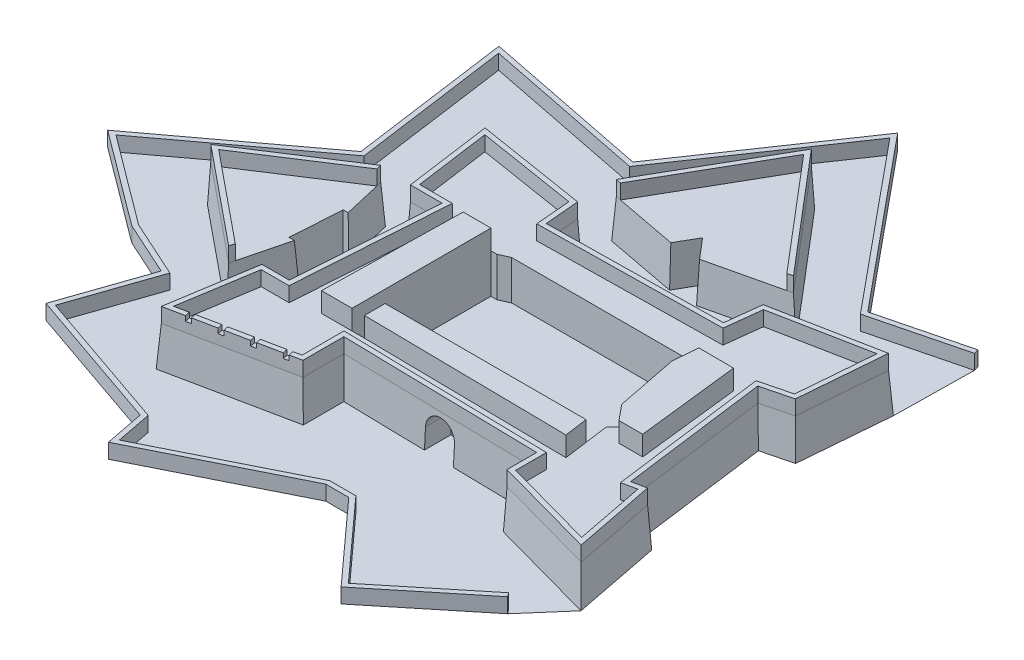
SolidWorks part; units mm, degrees
note: The reader was unsure of these and kept them because the rebuilt part matched: shared geometry of "Sketch5<4>", "Sketch5<6>", "Sketch7<4>", "Sketch7<6>".
material "Ceramic Porcelain"
ref_plane "Front Plane" through (0, 0, 0) normal (0, 0, 1) x (1, 0, 0)
ref_plane "Top Plane" through (0, 0, 0) normal (0, 1, 0) x (1, 0, 0)
ref_plane "Right Plane" through (0, 0, 0) normal (1, 0, 0) x (0, 0, -1)
sketch "Sketch5" plane through (0, 0, 0) normal (0, 1, 0) x (1, 0, 0)
  line L0 (24221.1472, 12812.7772) -> (25709.497, 22090.1576)
  line L1 (25709.497, 22090.1576) -> (28473.8169, 22090.1576)
  line L2 (28473.8169, 22090.1576) -> (29430.1682, 36196.3384)
  line L3 (29430.1682, 36196.3384) -> (26254.1998, 36196.3384)
  line L4 (26254.1998, 36196.3384) -> (24972.577, 45446.6988)
  line L5 (24972.577, 45446.6988) -> (36613.3827, 43579.1898)
  line L6 (36613.3827, 43579.1898) -> (36920.5122, 40112.6097)
  line L7 (36920.5122, 40112.6097) -> (54258.5673, 40378.764)
  line L8 (54258.5673, 40378.764) -> (54681.4749, 43954.2552)
  line L9 (54681.4749, 43954.2552) -> (65747.3221, 46120.0937)
  line L10 (65747.3221, 46120.0937) -> (64980.7856, 36956.7795)
  line L11 (64980.7856, 36956.7795) -> (61977.0436, 36196.3384)
  line L12 (61977.0436, 36196.3384) -> (63878.1461, 21747.9592)
  line L13 (63878.1461, 21747.9592) -> (65285.6599, 22049.5692)
  line L14 (65285.6599, 22049.5692) -> (67033.9764, 13116.9536)
  line L15 (67033.9764, 13116.9536) -> (56159.6698, 16120.6957)
  line L16 (56159.6698, 16120.6957) -> (56159.6698, 19081.3266)
  line L17 (56159.6698, 19081.3266) -> (36613.3827, 19466.6361)
  line L18 (36613.3827, 19466.6361) -> (36613.3827, 15360.2546)
  line L19 (36613.3827, 15360.2546) -> (24221.1472, 12812.7772)
  line L20 (-1773.6346, 178.1498) -> (-1176.968, 178.1498) construction
  line L21 (22700.2652, 21443.7828) -> (12396.2895, 29846.656)
  line L22 (12396.2895, 29846.656) -> (23346.6401, 36956.7795)
  line L23 (23346.6401, 36956.7795) -> (24487.3016, 32089.957)
  line L24 (24487.3016, 32089.957) -> (23916.9708, 32089.957)
  line L25 (23916.9708, 32089.957) -> (23612.7944, 27337.2006)
  line L26 (23612.7944, 27337.2006) -> (24202.1362, 27337.2006)
  line L27 (24202.1362, 27337.2006) -> (22700.2652, 21443.7828)
  line L28 (36084.0271, 47184.7111) -> (43604.7887, 60268.0988)
  line L29 (43604.7887, 60268.0988) -> (54258.5673, 47720.822)
  line L30 (54258.5673, 47720.822) -> (46076.764, 45803.2119)
  line L31 (46076.764, 45803.2119) -> (44448.5387, 47720.822)
  line L32 (44448.5387, 47720.822) -> (43346.2333, 45803.2119)
  line L33 (43346.2333, 45803.2119) -> (36084.0271, 47184.7111)
  line L34 (54258.5673, 1546.8436) -> (63580.1829, 9139.4247)
  line L35 (54258.5673, 1546.8436) -> (46779.4578, 9805.0782)
  line L36 (46779.4578, 9805.0782) -> (44448.5387, 9805.0782)
  line L37 (44448.5387, 9805.0782) -> (29734.3446, 2459.3728)
  line L38 (29734.3446, 2459.3728) -> (28951.9926, 6456.6182)
  line L39 (28951.9926, 6456.6182) -> (14358.2273, 11493.4121)
  line L40 (14358.2273, 11493.4121) -> (15582.0398, 15039.3251)
  line L41 (15582.0398, 15039.3251) -> (17356.6178, 20181.0432)
  line L42 (17356.6178, 20181.0432) -> (11903.5237, 22658.2071)
  line L43 (11903.5237, 22658.2071) -> (2267.2151, 29846.656)
  line L44 (2267.2151, 29846.656) -> (16995.4367, 40821.5186)
  line L45 (16995.4367, 40821.5186) -> (14741.9326, 57086.6197)
  line L46 (14741.9326, 57086.6197) -> (31723.6583, 53702.451)
  line L47 (31723.6583, 53702.451) -> (42609.1401, 69687.8824)
  line L48 (42609.1401, 69687.8824) -> (56817.3793, 52446.1339)
  line L49 (56817.3793, 52446.1339) -> (65747.3221, 54706.8789)
  line L50 (56632.9822, 51883.6769) -> (65870.0331, 54222.1708)
  line L51 (31723.721, 22093.3415) -> (32001.7288, 36196.3384)
  line L52 (32001.7288, 36196.3384) -> (35428.9681, 36196.3384)
  line L53 (35428.9681, 36196.3384) -> (35428.9681, 22093.3415)
  line L54 (35428.9681, 22093.3415) -> (31723.721, 22093.3415)
  line L55 (36084.0271, 22093.3415) -> (36084.0271, 26560.0447)
  line L56 (36084.0271, 26560.0447) -> (56159.6698, 26560.0447)
  line L57 (56159.6698, 26560.0447) -> (56817.3793, 21812.8994)
  line L58 (56817.3793, 21812.8994) -> (36084.0271, 22093.3415)
  line L59 (60646.2718, 25773.5818) -> (58239.847, 25773.5818)
  line L60 (58239.847, 25773.5818) -> (56951.3309, 27337.2006)
  line L61 (56951.3309, 27337.2006) -> (55973.2334, 34396.8086)
  line L62 (55973.2334, 34396.8086) -> (55973.2334, 36196.3384)
  line L63 (55973.2334, 36196.3384) -> (59443.0594, 36196.3384)
  line L64 (59443.0594, 36196.3384) -> (60646.2718, 25773.5818)
  line L65 (35428.9681, 36196.3384) -> (36458.7307, 36657.9549)
  line L66 (36458.7307, 36657.9549) -> (54258.5673, 36657.9549)
  line L67 (54258.5673, 36657.9549) -> (55973.2334, 36196.3384)
  line L68 (56951.3309, 27337.2006) -> (56159.6698, 26560.0447)
  line L69 (36084.0271, 22093.3415) -> (35428.9681, 22093.3415)
  line L70 (42647.2108, 68855.4598) -> (56632.9822, 51883.6769)
  line L71 (31950.6039, 53147.3929) -> (42647.2108, 68855.4598)
  line L72 (15333.6835, 56458.862) -> (31950.6039, 53147.3929)
  line L73 (17531.2836, 40597.259) -> (15333.6835, 56458.862)
  line L74 (3103.7229, 29846.4364) -> (17531.2836, 40597.259)
  line L75 (12159.3372, 23091.1711) -> (3103.7229, 29846.4364)
  line L76 (17977.7189, 20448.069) -> (12159.3372, 23091.1711)
  line L77 (16054.6817, 14876.2006) -> (17977.7189, 20448.069)
  line L78 (14993.9937, 11802.9296) -> (16054.6817, 14876.2006)
  line L79 (29387.3629, 6835.299) -> (14993.9937, 11802.9296)
  line L80 (30098.8383, 3200.1815) -> (29387.3629, 6835.299)
  line L81 (44330.6682, 10305.0782) -> (30098.8383, 3200.1815)
  line L82 (47001.2063, 10305.0782) -> (44330.6682, 10305.0782)
  line L83 (54310.675, 2234.1565) -> (47001.2063, 10305.0782)
  line L84 (54310.675, 2234.1565) -> (63264.4166, 9527.0994)
  line L85 (65747.3221, 54706.8789) -> (65870.0331, 54222.1708)
  line L86 (63580.1829, 9139.4247) -> (63264.4166, 9527.0994)
  line L87 (63580.1829, 9139.4247) -> (67033.9764, 13116.9536)
  line L88 (65870.0331, 54222.1708) -> (65747.3221, 46120.0937)
  dimension "D1" = 19546.2871
  dimension "D2" = 500
extrude "Boss-Extrude2" add sketch "Sketch5" along normal blind 4000 draft 3 contours L19 L18 L17 L16 L15 L14 L13 L12 L11 L10 L9 L8 L7 L6 L5 L4 L3 L2 L1 L0 L58 L69 L54 L51 L52 L65 L66 L67 L63 L64 L59 L60 L68 L57 | L33 L32 L31 L30 L29 L28 | L27 L26 L25 L24 L23 L22 L21 | L69 L55 L56 L68 L61 L62 L67 L66 L65 L53 | L54 L53 L52 L51 | L58 L57 L56 L55 | L64 L63 L62 L61 L60 L59
extrude "Cut-Extrude8" cut sketch "Sketch5<4>" against normal blind 9000 and the other way through all contours L54 L53 L52 L51 | L69 L55 L56 L68 L61 L62 L67 L66 L65 L53 | L64 L63 L62 L61 L60 L59 | L58 L57 L56 L55
sketch "Sketch5<4>" plane through (0, 0, 0) normal (0, 1, 0) x (1, 0, 0) same geometry as "Sketch5"
extrude "Boss-Extrude8" add sketch "Sketch5<6>" along normal blind 1500 separate body contours L34 L86 L84 L83 L82 L81 L80 L79 L78 L77 L76 L75 L74 L73 L72 L71 L70 L50 L85 L49 L48 L47 L46 L45 L44 L43 L42 L41 L40 L39 L38 L37 L36 L35
sketch "Sketch5<6>" plane through (0, 0, 0) normal (0, 1, 0) x (1, 0, 0) same geometry as "Sketch5"
sketch "Sketch7" plane through (0, 0, 0) normal (0, 1, 0) x (1, 0, 0)
  line L0 (36412.5629, 47335.6038) -> (43238.8427, 46037.0314) construction
  line L1 (43238.8427, 46037.0314) -> (44415.3723, 48083.7647) construction
  line L2 (44415.3723, 48083.7647) -> (46153.6491, 46036.5437) construction
  line L3 (46153.6491, 46036.5437) -> (53876.7307, 47846.6409) construction
  line L4 (53876.7307, 47846.6409) -> (43637.955, 59905.1561) construction
  line L5 (43637.955, 59905.1561) -> (36412.5629, 47335.6038) construction
  line L6 (24476.2044, 13079.2242) -> (36403.7516, 15531.1754) construction
  line L7 (36403.7516, 15531.1754) -> (36403.7516, 19680.4403) construction
  line L8 (36403.7516, 19680.4403) -> (56369.301, 19286.866) construction
  line L9 (56369.301, 19286.866) -> (56369.301, 16280.2721) construction
  line L10 (56369.301, 16280.2721) -> (66763.1605, 13409.2409) construction
  line L11 (66763.1605, 13409.2409) -> (65120.9215, 21799.8781) construction
  line L12 (65120.9215, 21799.8781) -> (63699.9419, 21495.3825) construction
  line L13 (63699.9419, 21495.3825) -> (61744.8858, 36353.809) construction
  line L14 (61744.8858, 36353.809) -> (64784.3517, 37123.294) construction
  line L15 (64784.3517, 37123.294) -> (65515.2909, 45861.0713) construction
  line L16 (65515.2909, 45861.0713) -> (54871.7056, 43777.879) construction
  line L17 (54871.7056, 43777.879) -> (54445.2006, 40171.9732) construction
  line L18 (54445.2006, 40171.9732) -> (36728.8955, 39900.0124) construction
  line L19 (36728.8955, 39900.0124) -> (36418.9775, 43398.0662) construction
  line L20 (36418.9775, 43398.0662) -> (25219.1056, 45194.8371) construction
  line L21 (25219.1056, 45194.8371) -> (26436.7893, 36405.9696) construction
  line L22 (26436.7893, 36405.9696) -> (29654.4928, 36405.9696) construction
  line L23 (29654.4928, 36405.9696) -> (28669.717, 21880.5265) construction
  line L24 (28669.717, 21880.5265) -> (25888.178, 21880.5265) construction
  line L25 (25888.178, 21880.5265) -> (24476.2044, 13079.2242) construction
  line L26 (22578.2296, 21813.8029) -> (23932.383, 27127.5695) construction
  line L27 (23932.383, 27127.5695) -> (23389.318, 27127.5695) construction
  line L28 (23389.318, 27127.5695) -> (23720.3272, 32299.5881) construction
  line L29 (23720.3272, 32299.5881) -> (24222.8575, 32299.5881) construction
  line L30 (24222.8575, 32299.5881) -> (23210.6102, 36618.5097) construction
  line L31 (23210.6102, 36618.5097) -> (12751.5897, 29827.4096) construction
  line L32 (12751.5897, 29827.4096) -> (22578.2296, 21813.8029) construction
  line L33 (36412.5629, 47335.6038) -> (43238.8427, 46037.0314) construction
  line L34 (43238.8427, 46037.0314) -> (44415.3723, 48083.7647) construction
  line L35 (44415.3723, 48083.7647) -> (46153.6491, 46036.5437) construction
  line L36 (46153.6491, 46036.5437) -> (53876.7307, 47846.6409) construction
  line L37 (53876.7307, 47846.6409) -> (43637.955, 59905.1561)
  line L38 (43637.955, 59905.1561) -> (36412.5629, 47335.6038)
  line L39 (24476.2044, 13079.2242) -> (36403.7516, 15531.1754)
  line L40 (36403.7516, 15531.1754) -> (36403.7516, 19680.4403)
  line L41 (36403.7516, 19680.4403) -> (56369.301, 19286.866)
  line L42 (56369.301, 19286.866) -> (56369.301, 16280.2721)
  line L43 (56369.301, 16280.2721) -> (66763.1605, 13409.2409)
  line L44 (66763.1605, 13409.2409) -> (65120.9215, 21799.8781)
  line L45 (65120.9215, 21799.8781) -> (63699.9419, 21495.3825)
  line L46 (63699.9419, 21495.3825) -> (61744.8858, 36353.809)
  line L47 (61744.8858, 36353.809) -> (64784.3517, 37123.294)
  line L48 (64784.3517, 37123.294) -> (65515.2909, 45861.0713)
  line L49 (65515.2909, 45861.0713) -> (54871.7056, 43777.879)
  line L50 (54871.7056, 43777.879) -> (54445.2006, 40171.9732)
  line L51 (54445.2006, 40171.9732) -> (36728.8955, 39900.0124)
  line L52 (36728.8955, 39900.0124) -> (36418.9775, 43398.0662)
  line L53 (36418.9775, 43398.0662) -> (25219.1056, 45194.8371)
  line L54 (25219.1056, 45194.8371) -> (26436.7893, 36405.9696)
  line L55 (26436.7893, 36405.9696) -> (29654.4928, 36405.9696)
  line L56 (29654.4928, 36405.9696) -> (28669.717, 21880.5265)
  line L57 (28669.717, 21880.5265) -> (25888.178, 21880.5265)
  line L58 (25888.178, 21880.5265) -> (24476.2044, 13079.2242)
  line L59 (22578.2296, 21813.8029) -> (23932.383, 27127.5695) construction
  line L60 (23932.383, 27127.5695) -> (23389.318, 27127.5695) construction
  line L61 (23389.318, 27127.5695) -> (23720.3272, 32299.5881) construction
  line L62 (23720.3272, 32299.5881) -> (24222.8575, 32299.5881) construction
  line L63 (24222.8575, 32299.5881) -> (23210.6102, 36618.5097) construction
  line L64 (23210.6102, 36618.5097) -> (12751.5897, 29827.4096)
  line L65 (12751.5897, 29827.4096) -> (22578.2296, 21813.8029)
  line L66 (23331.879, 36101.0963) -> (13599.0312, 29781.5042)
  line L67 (13599.0312, 29781.5042) -> (22714.3568, 22347.973)
  line L70 (53329.6724, 47718.4241) -> (43717.0615, 59039.4862)
  line L71 (43717.0615, 59039.4862) -> (36932.436, 47236.7076)
  line L72 (25807.1113, 44594.1112) -> (26872.2912, 36905.9696)
  line L73 (26872.2912, 36905.9696) -> (30189.5389, 36905.9696)
  line L74 (30189.5389, 36905.9696) -> (29136.9665, 21380.5265)
  line L75 (29136.9665, 21380.5265) -> (26314.3575, 21380.5265)
  line L76 (26314.3575, 21380.5265) -> (25084.5518, 13714.7379)
  line L77 (25084.5518, 13714.7379) -> (35903.7516, 15938.8456)
  line L78 (35903.7516, 15938.8456) -> (35903.7516, 20190.3938)
  line L79 (35903.7516, 20190.3938) -> (56869.301, 19777.1068)
  line L80 (56869.301, 19777.1068) -> (56869.301, 16660.8845)
  line L81 (56869.301, 16660.8845) -> (66117.2261, 14106.3877)
  line L82 (66117.2261, 14106.3877) -> (64727.9972, 21204.3293)
  line L83 (64727.9972, 21204.3293) -> (63274.8995, 20892.9512)
  line L84 (63274.8995, 20892.9512) -> (61191.1564, 36729.3986)
  line L85 (61191.1564, 36729.3986) -> (64315.8289, 37520.4549)
  line L86 (64315.8289, 37520.4549) -> (64961.8634, 45243.266)
  line L87 (64961.8634, 45243.266) -> (55325.4328, 43357.197)
  line L88 (55325.4328, 43357.197) -> (54890.3474, 39678.7477)
  line L89 (54890.3474, 39678.7477) -> (36271.8623, 39392.9376)
  line L90 (36271.8623, 39392.9376) -> (35955.2935, 42966.0606)
  line L91 (35955.2935, 42966.0606) -> (25807.1113, 44594.1112)
  line L92 (13599.0312, 29781.5042) -> (22894.2252, 22201.2907) construction
  line L93 (23932.383, 27127.5695) -> (22578.2296, 21813.8029) construction
  line L94 (23482.8996, 36199.1549) -> (13599.0312, 29781.5042) construction
  line L95 (23210.6102, 36618.5097) -> (24222.8575, 32299.5881) construction
  line L96 (43717.0615, 59039.4862) -> (36846.0473, 47086.4226) construction
  line L97 (53495.5901, 47523.0179) -> (43717.0615, 59039.4862) construction
  line L98 (53329.6724, 47718.4241) -> (53876.7307, 47846.6409)
  line L99 (36932.436, 47236.7076) -> (36412.5629, 47335.6038)
  line L100 (23331.879, 36101.0963) -> (23210.6102, 36618.5097)
  line L101 (22714.3568, 22347.973) -> (22578.2296, 21813.8029)
  dimension "D1" = 500
  dimension "D2" = 500
  dimension "D3" = 500
extrude "Boss-Extrude3" add sketch "Sketch7" along normal blind 1500 from surface at 4000 contours L99 L71 L70 L98 L37 L38 starting at face at (44622.5188, 4000, -49207.4567)
extrude "Boss-Extrude4" add sketch "Sketch7<4>" along normal blind 1500 from surface at 4000 contours L57 L58 L39 L40 L41 L42 L43 L44 L45 L46 L47 L48 L49 L50 L51 L52 L53 L54 L55 L56 L91 L90 L89 L88 L87 L86 L85 L84 L83 L82 L81 L80 L79 L78 L77 L76 L75 L74 L73 L72 starting at face at (48475.8873, 4000, -29965.0196)
sketch "Sketch7<4>" plane through (0, 0, 0) normal (0, 1, 0) x (1, 0, 0) same geometry as "Sketch7"
extrude "Boss-Extrude5" add sketch "Sketch7<6>" along normal blind 1500 from surface at 4000 contours L64 L65 L101 L67 L66 L100 starting at face at (21972.1879, 4000, -29587.7196)
sketch "Sketch7<6>" plane through (0, 0, 0) normal (0, 1, 0) x (1, 0, 0) same geometry as "Sketch7"
ref_plane "Plane1" through (0, 0, -30000) normal (0, 0, 1) x (1, 0, 0)
sketch "Sketch9" plane through (0, 0, -30000) normal (0, 0, 1) x (1, 0, 0)
  line L0 (44964.6369, 0) -> (44964.6369, 2000)
  line L1 (46779.4578, 0) -> (44448.5387, 0) construction
  line L3 (47964.6369, 2000) -> (47964.6369, 0)
  line L4 (54258.5673, 0) -> (46779.4578, 0) construction
  line L5 (47964.6369, 0) -> (44964.6369, 0)
  arc A0 (47964.6369, 2000) -> (44964.6369, 2000) centre (46464.6369, 2000) ccw
  point P10 (0, 0)
  dimension "D2" = 1500
  dimension "D1" = 2000
extrude "Cut-Extrude9" cut sketch "Sketch9" along normal blind 11000
sketch "Sketch10" plane through (0, 0, 0) normal (0, 1, 0) x (1, 0, 0)
  line L0 (65747.3221, 46120.0937) -> (65870.0331, 54222.1708)
  line L1 (63580.1829, 9139.4247) -> (67033.9764, 13116.9536)
  line L2 (67033.9764, 13116.9536) -> (65285.6599, 22049.5692)
  line L3 (65285.6599, 22049.5692) -> (63878.1461, 21747.9592)
  line L4 (63878.1461, 21747.9592) -> (61977.0436, 36196.3384)
  line L5 (61977.0436, 36196.3384) -> (64980.7856, 36956.7795)
  line L6 (64980.7856, 36956.7795) -> (65747.3221, 46120.0937)
  line L34 (54258.5673, 1546.8436) -> (63580.1829, 9139.4247)
  line L35 (46779.4578, 9805.0782) -> (54258.5673, 1546.8436)
  line L36 (44448.5387, 9805.0782) -> (46779.4578, 9805.0782)
  line L37 (29734.3446, 2459.3728) -> (44448.5387, 9805.0782)
  line L38 (28951.9926, 6456.6182) -> (29734.3446, 2459.3728)
  line L39 (14358.2273, 11493.4121) -> (28951.9926, 6456.6182)
  line L40 (17356.6178, 20181.0432) -> (14358.2273, 11493.4121)
  line L41 (11903.5237, 22658.2071) -> (17356.6178, 20181.0432)
  line L42 (2267.2151, 29846.656) -> (11903.5237, 22658.2071)
  line L43 (16995.4367, 40821.5186) -> (2267.2151, 29846.656)
  line L44 (14741.9326, 57086.6197) -> (16995.4367, 40821.5186)
  line L45 (31723.6583, 53702.451) -> (14741.9326, 57086.6197)
  line L46 (42609.1401, 69687.8824) -> (31723.6583, 53702.451)
  line L47 (56817.3793, 52446.1339) -> (42609.1401, 69687.8824)
  line L48 (65747.3221, 54706.8789) -> (56817.3793, 52446.1339)
  line L49 (65870.0331, 54222.1708) -> (65747.3221, 54706.8789)
  line L50 (56632.9822, 51883.6769) -> (65870.0331, 54222.1708)
  line L51 (42647.2108, 68855.4598) -> (56632.9822, 51883.6769)
  line L52 (31950.6039, 53147.3929) -> (42647.2108, 68855.4598)
  line L53 (15333.6835, 56458.862) -> (31950.6039, 53147.3929)
  line L54 (17531.2836, 40597.259) -> (15333.6835, 56458.862)
  line L55 (3103.7229, 29846.4364) -> (17531.2836, 40597.259)
  line L56 (12159.3372, 23091.1711) -> (3103.7229, 29846.4364)
  line L57 (17977.7189, 20448.069) -> (12159.3372, 23091.1711)
  line L58 (14993.9937, 11802.9296) -> (17977.7189, 20448.069)
  line L59 (29387.3629, 6835.299) -> (14993.9937, 11802.9296)
  line L60 (30098.8383, 3200.1815) -> (29387.3629, 6835.299)
  line L61 (44330.6682, 10305.0782) -> (30098.8383, 3200.1815)
  line L62 (47001.2063, 10305.0782) -> (44330.6682, 10305.0782)
  line L63 (54310.675, 2234.1565) -> (47001.2063, 10305.0782)
  line L64 (63264.4166, 9527.0994) -> (54310.675, 2234.1565)
  line L65 (63580.1829, 9139.4247) -> (63264.4166, 9527.0994)
  line L82 (56632.9822, 51883.6769) -> (65870.0331, 54222.1708)
  line L83 (42647.2108, 68855.4598) -> (56632.9822, 51883.6769)
  line L84 (31950.6039, 53147.3929) -> (42647.2108, 68855.4598)
  line L85 (15333.6835, 56458.862) -> (31950.6039, 53147.3929)
  line L86 (17531.2836, 40597.259) -> (15333.6835, 56458.862)
  line L87 (3103.7229, 29846.4364) -> (17531.2836, 40597.259)
  line L88 (12159.3372, 23091.1711) -> (3103.7229, 29846.4364)
  line L89 (17977.7189, 20448.069) -> (12159.3372, 23091.1711)
  line L90 (14993.9937, 11802.9296) -> (17977.7189, 20448.069)
  line L91 (29387.3629, 6835.299) -> (14993.9937, 11802.9296)
  line L92 (30098.8383, 3200.1815) -> (29387.3629, 6835.299)
  line L93 (44330.6682, 10305.0782) -> (30098.8383, 3200.1815)
  line L94 (47001.2063, 10305.0782) -> (44330.6682, 10305.0782)
  line L95 (54310.675, 2234.1565) -> (47001.2063, 10305.0782)
  line L96 (63264.4166, 9527.0994) -> (54310.675, 2234.1565)
  line L97 (63580.1829, 9139.4247) -> (63264.4166, 9527.0994)
  dimension "D1" = 0
surface "Surface-Plane3" sketch "Sketch10"
sketch "Sketch12" plane through (-1587.2797, 0, -7721.3421) normal (0.2014, 0, 0.9795) x (0.9795, 0, -0.2014)
  line L0 (38785.4607, 5500) -> (26608.4968, 5500) construction
  line L1 (37590.8183, 5500) -> (37090.8183, 5500)
  line L2 (37590.8183, 5500) -> (37590.8183, 5000)
  line L3 (37590.8183, 5000) -> (37090.8183, 5000)
  line L4 (37090.8183, 5500) -> (37090.8183, 5000)
  dimension "D1" = 500
  dimension "D2" = 500
extrude "Cut-Extrude10" cut sketch "Sketch12" against normal up to next (500 mm away)
pattern_linear "LPattern1" count 4 spacing 2800 along (-0.9795, 0, 0.2014) of "Cut-Extrude10"
sketch "Sketch8" plane through (0, 0, 0) normal (0, 1, 0) x (1, 0, 0)
  line L1 (32001.7288, 36196.3384) -> (34821.1895, 36196.3384)
  line L2 (32001.7288, 36196.3384) -> (31723.721, 22093.3415)
  line L3 (31723.721, 22093.3415) -> (34821.1895, 22093.3415)
  line L4 (34821.1895, 36196.3384) -> (34821.1895, 22093.3415)
  line L6 (36084.0271, 22093.3415) -> (56817.3793, 21812.8994)
  line L7 (36084.0271, 22093.3415) -> (36084.0271, 24186.472)
  line L8 (36084.0271, 24186.472) -> (56488.5246, 24186.472)
  line L9 (56817.3793, 21812.8994) -> (56488.5246, 24186.472)
  line L11 (59443.0594, 36196.3384) -> (60646.2718, 25773.5818)
  line L13 (60646.2718, 25773.5818) -> (58239.847, 25773.5818)
  line L14 (58239.847, 25773.5818) -> (56951.3309, 27337.2006)
  line L15 (56951.3309, 27337.2006) -> (55694.2856, 33692.8293)
  line L16 (55694.2856, 33692.8293) -> (55908.7204, 36213.7064)
  line L17 (55908.7204, 36213.7064) -> (59443.0594, 36196.3384)
  line L18 (32001.7288, 36196.3384) -> (35428.9681, 36196.3384) construction
  line L19 (36084.0271, 22093.3415) -> (31723.721, 22093.3415) construction
  line L20 (56159.6698, 26560.0447) -> (56817.3793, 21812.8994) construction
  line L21 (54258.5673, 36657.9549) -> (55973.2334, 36196.3384) construction
  point P5 (31723.721, 22093.3415)
  point P6 (34800.9739, 22093.3415)
  point P12 (56488.5246, 24186.472)
  point P14 (55694.2856, 33692.8293)
  point P18 (34866.0621, 22093.3415)
  point P19 (32001.7288, 36196.3384)
  point P23 (60646.2718, 25773.5818)
  point P24 (59443.0594, 36196.3384)
  point P29 (31723.721, 22093.3415)
  point P32 (34800.9739, 36196.3384)
  point P33 (34792.6192, 36196.3384)
  point P36 (34821.1895, 22093.3415)
  point P39 (36084.0271, 22093.3415)
  point P44 (55906.3386, 36196.3384)
  point P45 (55973.2334, 36196.3384)
extrude "Boss-Extrude7" add sketch "Sketch8" along normal blind 6000
equation "\"D3@Sketch1\"=\"D2@Sketch1\""
equation "\"D4@Sketch1\"=\"D2@Sketch1\""
equation "\"D5@Sketch1\"=\"D2@Sketch1\""
equation "\"D7@Sketch1\"=\"D6@Sketch1\""
equation "\"D8@Sketch1\"=\"D6@Sketch1\""
equation "\"D10@Sketch1\"=\"D6@Sketch1\""
equation "\"D11@Sketch1\"=\"D9@Sketch1\""
equation "\"D4@Sketch2\"=\"D3@Sketch2\""
equation "\"D5@Sketch2\"=\"D3@Sketch2\""
equation "\"D6@Sketch2\"=\"D3@Sketch2\""
